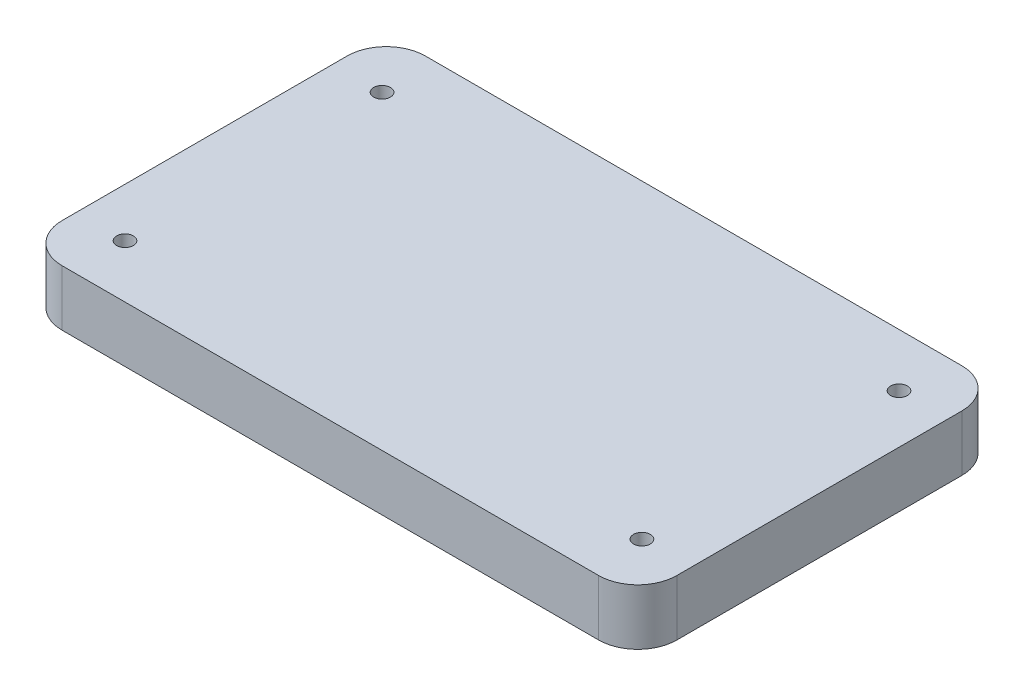
SolidWorks part; units mm, degrees
ref_plane "Front Plane" through (0, 0, 0) normal (0, 0, 1) x (1, 0, 0)
ref_plane "Top Plane" through (0, 0, 0) normal (0, 1, 0) x (1, 0, 0)
ref_plane "Right Plane" through (0, 0, 0) normal (1, 0, 0) x (0, 0, -1)
sketch "Sketch1" plane through (0, 0, 0) normal (0, 1, 0) x (1, 0, 0)
  line L1 (48, -32.5) -> (-48, -32.5)
  line L2 (55, -25.5) -> (55, 25.5)
  line L3 (48, 32.5) -> (-48, 32.5)
  line L4 (-55, -25.5) -> (-55, 25.5)
  line L5 (55, -32.5) -> (-55, 32.5) construction
  line L6 (55, 32.5) -> (-55, -32.5) construction
  line L7 (46.25, -23) -> (-46.25, -23) construction
  line L8 (46.25, -23) -> (46.25, 23) construction
  line L9 (46.25, 23) -> (-46.25, 23) construction
  line L10 (-46.25, -23) -> (-46.25, 23) construction
  line L11 (46.25, -23) -> (-46.25, 23) construction
  line L12 (46.25, 23) -> (-46.25, -23) construction
  circle A0 centre (-46.25, 23) radius 1.5
  circle A1 centre (-46.25, -23) radius 1.5
  circle A2 centre (46.25, -23) radius 1.5
  circle A3 centre (46.25, 23) radius 1.5
  arc A4 (-48, -32.5) -> (-55, -25.5) centre (-48, -25.5) cw
  arc A5 (48, -32.5) -> (55, -25.5) centre (48, -25.5) ccw
  arc A6 (55, 25.5) -> (48, 32.5) centre (48, 25.5) ccw
  arc A7 (-48, 32.5) -> (-55, 25.5) centre (-48, 25.5) ccw
  point P0 (0, 0)
  point P6 (0, 0)
  dimension "D5" = 7
  dimension "D1" = 110
  dimension "D2" = 65
  dimension "D3" = 92.5
  dimension "D4" = 46
extrude "Boss-Extrude1" add sketch "Sketch1" along normal mid plane 10
